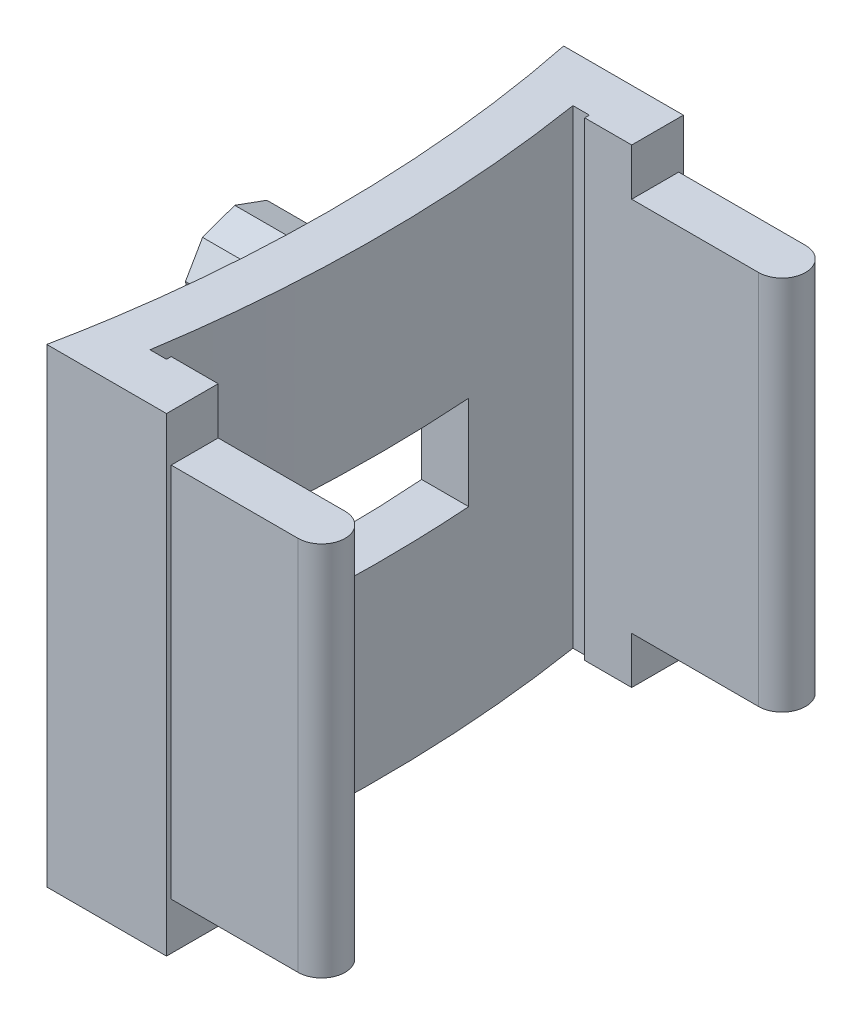
SolidWorks part; units mm, degrees
ref_plane "Front Plane" through (0, 0, 0) normal (0, 0, 1) x (1, 0, 0)
ref_plane "Top Plane" through (0, 0, 0) normal (0, 1, 0) x (1, 0, 0)
ref_plane "Right Plane" through (0, 0, 0) normal (1, 0, 0) x (0, 0, -1)
sketch "Sketch1" plane through (0, 0, 0) normal (0, 1, 0) x (1, 0, 0)
  line L0 (-15, 79.6562) -> (15, 79.6562)
  line L9 (-15, 75.1314) -> (-42.5, 27.5)
  line L10 (-42.5, 27.5) -> (-42.5, -27.5)
  line L11 (-42.5, -27.5) -> (-15, -75.1314)
  line L12 (-15, -75.1314) -> (15, -75.1314)
  line L13 (15, -75.1314) -> (42.5, -27.5)
  line L14 (42.5, -27.5) -> (42.5, 27.5)
  line L15 (42.5, 27.5) -> (15, 75.1314)
  line L16 (15, 75.1314) -> (-15, 75.1314)
  line L17 (-49.2865, 0) -> (49.2865, 0) construction
  line L18 (-15, 75.1314) -> (-15, 79.6562) construction
  line L19 (15, 75.1314) -> (15, 79.6562) construction
  line L20 (-15, 75.1314) -> (-18.7805, 77.3141) construction
  line L21 (-42.5, 27.5) -> (-46.1003, 29.5787) construction
  line L22 (-42.5, 27.5) -> (-46.5452, 27.5) construction
  line L23 (-42.5, -27.5) -> (-46.5452, -27.5) construction
  line L24 (-42.5, -27.5) -> (-46.1003, -29.5787) construction
  line L25 (-15, -75.1314) -> (-18.7805, -77.3141) construction
  line L26 (-15, -75.1314) -> (-15, -79.6562) construction
  line L27 (15, -75.1314) -> (15, -79.6562) construction
  line L28 (15, -75.1314) -> (18.7805, -77.3141) construction
  line L29 (42.5, -27.5) -> (46.1003, -29.5787) construction
  line L30 (42.5, -27.5) -> (46.5452, -27.5) construction
  line L31 (42.5, 27.5) -> (46.5452, 27.5) construction
  line L32 (42.5, 27.5) -> (46.1003, 29.5787) construction
  line L33 (15, 75.1314) -> (18.7805, 77.3141) construction
  line L34 (-15, -79.6562) -> (15, -79.6562)
  line L35 (18.7805, 77.3141) -> (46.1003, 29.5787) construction
  line L36 (46.5452, 27.5) -> (46.5452, -27.5) construction
  line L37 (46.1003, -29.5787) -> (18.7805, -77.3141) construction
  line L39 (-18.7805, -77.3141) -> (-46.1003, -29.5787) construction
  line L40 (-46.5452, -27.5) -> (-46.5452, 27.5) construction
  line L41 (-18.7805, 77.3141) -> (-46.1003, 29.5787) construction
  line L42 (0, 79.6562) -> (0, -79.6562) construction
  ellipse E0 centre (0, 0) end of major axis (0, 79.6261) minor radius 45.2865
  ellipse E1 centre (0, 0) end of major axis (0, 83.623) minor radius 49.2865 (-15, 79.6562) -> (-15, -79.6562) ccw
  ellipse E2 centre (0, 0) end of major axis (0, 83.623) minor radius 49.2865 (15, -79.6562) -> (15, 79.6562) ccw
  dimension "D1" = 55
  dimension "D2" = 30
  dimension "D3" = 150
  dimension "D4" = 150
  dimension "D5" = 150
  dimension "D6" = 150
  dimension "D7" = 90
ref_plane "Plane1" through (0, 0, 0) normal (0, 1, 0) x (1, 0, 0)
sketch "Sketch2" plane through (0, 0, 0) normal (0, 1, 0) x (1, 0, 0)
  line L0 (46.5452, 27.5) -> (49.2865, 27.5)
  line L1 (46.5452, -27.5) -> (49.2865, -27.5)
  line L2 (49.2865, 27.5) -> (49.2865, -27.5) construction
  line L4 (59.2865, -27.5) -> (59.2865, -27)
  line L5 (46.5452, 27.5) -> (46.5452, -27.5) construction
  line L6 (49.2865, 27.5) -> (59.2865, 27.5)
  line L7 (49.2865, -27.5) -> (59.2865, -27.5)
  line L9 (59.2865, 27) -> (59.2865, -27) construction
  line L10 (59.2865, 27) -> (75.2865, 27)
  line L11 (75.2865, 27) -> (75.2865, -27)
  line L12 (75.2865, -27) -> (59.2865, -27)
  line L13 (59.2865, 27.5) -> (59.2865, 27)
  ellipse E0 centre (0, 0) end of major axis (0, 83.623) minor radius 49.2865 (15, -79.6562) -> (15, 79.6562) ccw construction
  ellipse E1 centre (0, 0) end of major axis (0, 83.623) minor radius 49.2865 (46.5452, -27.5) -> (46.5452, 27.5) ccw
  dimension "D1" = 54
  dimension "D2" = 0.5
  dimension "D3" = 0.5
extrude "Boss-Extrude1" add sketch "Sketch2" along normal blind 50
shell "Shell1" thickness 5 removed face at (60.4439, 50, 0) removed face at (75.2865, 25, 0) removed face at (60.4439, 0, 0)
ref_plane "Plane2" through (46.5452, 0, 0) normal (-1, 0, 0) x (0, 0, 1)
sketch "Sketch3" plane through (46.5452, 0, 0) normal (-1, 0, 0) x (0, 0, 1)
  line L0 (0, 50) -> (0, 0) construction
  line L1 (27.5, 50) -> (-27.5, 50) construction
  line L2 (-27.5, 25) -> (27.5, 25) construction
  line L3 (-27.5, 50) -> (-27.5, 0) construction
  line L4 (27.5, 50) -> (27.5, 0) construction
  line L12 (-5.2401, 40.924) -> (-4.608, 37.3396)
  line L13 (-4.608, 37.3396) -> (-1.8199, 35)
  line L14 (-1.8199, 35) -> (1.8199, 35)
  line L15 (1.8199, 35) -> (4.608, 37.3396)
  line L16 (4.608, 37.3396) -> (5.2401, 40.924)
  line L17 (5.2401, 40.924) -> (3.4202, 44.076)
  line L18 (3.4202, 44.076) -> (0, 45.3209)
  line L19 (0, 45.3209) -> (-3.4202, 44.076)
  line L20 (-3.4202, 44.076) -> (-5.2401, 40.924)
  line L21 (0, 4.6791) -> (3.4202, 5.924)
  line L22 (3.4202, 5.924) -> (5.2401, 9.076)
  line L23 (5.2401, 9.076) -> (4.608, 12.6604)
  line L24 (4.608, 12.6604) -> (1.8199, 15)
  line L25 (1.8199, 15) -> (-1.8199, 15)
  line L26 (-1.8199, 15) -> (-4.608, 12.6604)
  line L27 (-4.608, 12.6604) -> (-5.2401, 9.076)
  line L28 (-5.2401, 9.076) -> (-3.4202, 5.924)
  line L29 (-3.4202, 5.924) -> (0, 4.6791)
  circle A0 centre (0, 40) radius 5 construction
  circle A1 centre (0, 10) radius 5 construction
  point P11 (0, 30)
  dimension "D1" = 10
  dimension "D2" = 10
extrude "Boss-Extrude2" add sketch "Sketch3" along normal blind 7.5 and the other way blind 5
sketch "Sketch4" plane through (46.5452, 0, 0) normal (-1, 0, 0) x (0, 0, 1)
  line L0 (0, 50) -> (0, 0) construction
  line L1 (27.5, 50) -> (-27.5, 50) construction
  line L2 (27.5, 25) -> (-27.5, 25) construction
  line L3 (27.5, 50) -> (27.5, 0) construction
  line L4 (-27.5, 50) -> (-27.5, 0) construction
  line L6 (-10, 30) -> (10, 30)
  line L7 (-10, 30) -> (-10, 20)
  line L8 (-10, 20) -> (10, 20)
  line L9 (10, 30) -> (10, 20)
  line L10 (-10, 30) -> (10, 20) construction
  line L11 (-10, 20) -> (10, 30) construction
  point P11 (0, 25)
  point P16 (63.4003, 41.4473)
extrude "Cut-Extrude1" cut sketch "Sketch4" against normal blind 10
ref_plane "Plane3" through (0, 0, 0) normal (0, 0, 1) x (1, 0, 0)
fillet "Fillet1" 2 edges at (75.2865, 25, -22) (75.2865, 25, -27) type full round first side face at (64.7865, 25, -22) second side face at (67.2865, 25, -27) middle face at (75.2865, 25, -24.5)
fillet "Fillet2" 2 edges at (75.2865, 25, 27) (75.2865, 25, 22) type full round first side face at (67.2865, 25, 27) second side face at (64.7865, 25, 22) middle face at (75.2865, 25, 24.5)
sketch "Sketch7" plane through (0, 0, 27) normal (0, 0, 1) x (1, 0, 0)
  line L0 (75.2865, 0) -> (75.2865, 50) construction
  line L1 (59.2865, 50) -> (75.2865, 50)
  line L2 (59.2865, 50) -> (59.2865, 45)
  line L3 (59.2865, 45) -> (75.2865, 45)
  line L4 (75.2865, 50) -> (75.2865, 45)
  line L6 (59.2865, 0) -> (75.2865, 0)
  line L7 (59.2865, 0) -> (59.2865, 5)
  line L8 (59.2865, 5) -> (75.2865, 5)
  line L9 (75.2865, 0) -> (75.2865, 5)
  dimension "D1" = 5
  dimension "D2" = 5
extrude "Cut-Extrude3" cut sketch "Sketch7" against normal blind 10
mirror "Mirror2" about plane through (0, 0, 0) normal (0, 0, 1) of "Cut-Extrude3"
